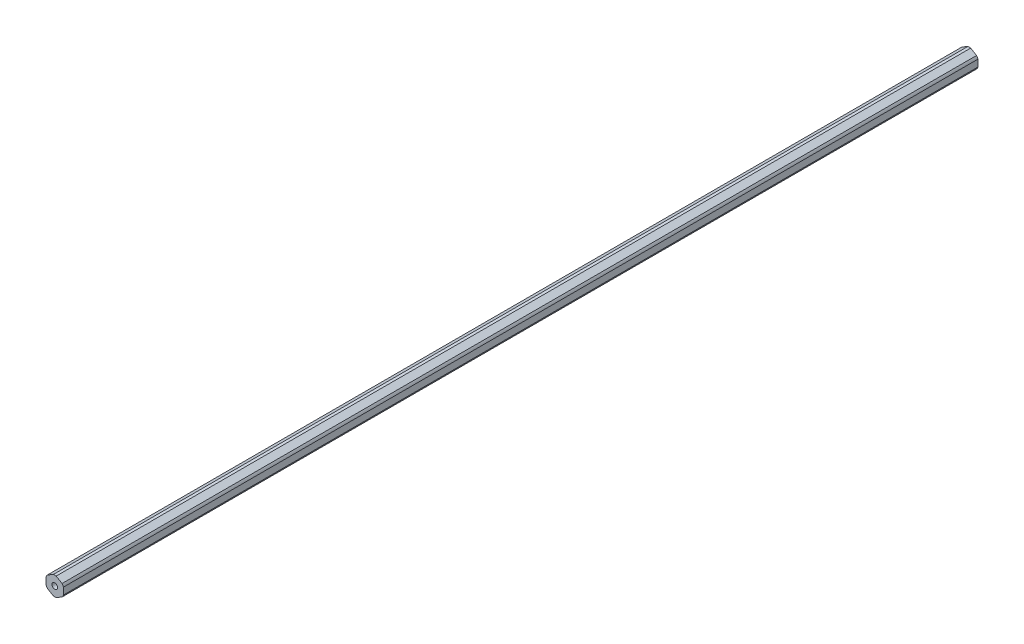
SolidWorks part; units mm, degrees
material "7075-T6 (SN)"
ref_plane "Front Plane" through (0, 0, 0) normal (0, 0, 1) x (1, 0, 0)
ref_plane "Top Plane" through (0, 0, 0) normal (0, 1, 0) x (1, 0, 0)
ref_plane "Right Plane" through (0, 0, 0) normal (1, 0, 0) x (0, 0, -1)
sketch "Sketch1" plane through (0, 0, 0) normal (0, 0, 1) x (1, 0, 0)
  line L1 (6.35, 3.6662) -> (0, 7.3323)
  line L2 (0, 7.3323) -> (-6.35, 3.6662)
  line L3 (-6.35, 3.6662) -> (-6.35, -3.6662)
  line L4 (-6.35, -3.6662) -> (0, -7.3323)
  line L5 (0, -7.3323) -> (6.35, -3.6662)
  line L6 (6.35, -3.6662) -> (6.35, 3.6662)
  circle A0 centre (0, 0) radius 6.35 construction
  circle A1 centre (0, 0) radius 6.8199
  dimension "D1" = 12.7
  dimension "D2" = 13.6398
extrude "Boss-Extrude1" add sketch "Sketch1" along normal blind 663.575 contours L6 A1 L1 L2 L3 L4 L5 region at (0, 0, 0)
hole_wizard "#10-32 Tapped Hole1" positions "Sketch2" profile "Sketch3" tap size "#10-32" standard "ANSI Inch"
sketch "Sketch2" plane through (0, 0, 663.575) normal (0, 0, 1) x (1, 0, 0)
  point P0 (0, 0)
sketch "Sketch3" plane through (0, 0, 663.575) normal (1, 0, 0) x (0, -1, 0)
  line L0 (0, 0) -> (0, 13.2428)
  line L1 (0, 13.2428) -> (2.0193, 12.0294)
  line L2 (2.0193, 12.0294) -> (2.0193, 0)
  line L5 (2.0193, 0) -> (0, 0)
  line L10 (0, 13.2428) -> (-2.0193, 12.0294) construction
  line L11 (0, -6.35) -> (0, 107.95) construction
  dimension "Tap Drill Dia." = 4.0386
  dimension "Tap Drill Depth" = 12.0294
  dimension "Drill Angle" = 118
cosmetic thread "Hole Thread1"
hole_wizard "#10-32 Tapped Hole2" positions "Sketch4" profile "Sketch5" tap size "#10-32" standard "ANSI Inch"
sketch "Sketch4" plane through (0, 0, 0) normal (0, 0, -1) x (-1, 0, 0)
  point P0 (0, 0)
sketch "Sketch5" plane through (0, 0, 0) normal (1, 0, 0) x (0, 1, 0)
  line L0 (0, 0) -> (0, 13.2428)
  line L1 (0, 13.2428) -> (2.0193, 12.0294)
  line L2 (2.0193, 12.0294) -> (2.0193, 0)
  line L5 (2.0193, 0) -> (0, 0)
  line L10 (0, 13.2428) -> (-2.0193, 12.0294) construction
  line L11 (0, -6.35) -> (0, 107.95) construction
  dimension "Tap Drill Dia." = 4.0386
  dimension "Tap Drill Depth" = 12.0294
  dimension "Drill Angle" = 118
cosmetic thread "Hole Thread2"
